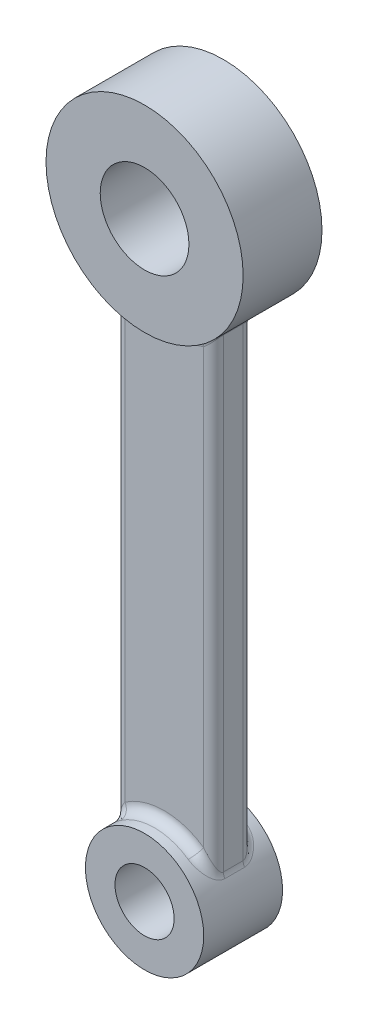
SolidWorks part; units mm, degrees
ref_plane "Front Plane" through (0, 0, 0) normal (0, 0, 1) x (1, 0, 0)
ref_plane "Top Plane" through (0, 0, 0) normal (0, 1, 0) x (1, 0, 0)
ref_plane "Right Plane" through (0, 0, 0) normal (1, 0, 0) x (0, 0, -1)
sketch "Sketch1" plane through (0, 0, 0) normal (0, 1, 0) x (1, 0, 0)
  line L1 (2.5, -1) -> (-2.5, -1)
  line L2 (2.5, -1) -> (2.5, 1)
  line L3 (2.5, 1) -> (-2.5, 1)
  line L4 (-2.5, -1) -> (-2.5, 1)
  line L5 (2.5, -1) -> (-2.5, 1) construction
  line L6 (2.5, 1) -> (-2.5, -1) construction
  point P0 (0, 0)
  dimension "D1" = 5
  dimension "D2" = 2
extrude "Boss-Extrude1" add sketch "Sketch1" along normal mid plane 30
sketch "Sketch2" plane through (0, 0, -1) normal (0, 0, -1) x (-1, 0, 0)
  line L0 (-2.5, -15) -> (2.5, -15) construction
  line L1 (-2.5, 15) -> (2.5, 15) construction
  circle A0 centre (0, -15) radius 3
  circle A1 centre (0, 15) radius 5
  dimension "D1" = 6
  dimension "D2" = 10
sketch "Sketch3" plane through (0, 0, 0) normal (0, 0, 1) x (1, 0, 0)
  circle A0 centre (0, -15) radius 3
  circle A1 centre (0, 15) radius 5
extrude "Boss-Extrude3" add sketch "Sketch3" along normal mid plane 4
sketch "Sketch4" plane through (0, 0, -2) normal (0, 0, -1) x (-1, 0, 0)
  circle A0 centre (0, -15) radius 1.5
  dimension "D1" = 3
extrude "Cut-Extrude1" cut sketch "Sketch4" against normal blind 7
sketch "Sketch5" plane through (0, 0, -2) normal (0, 0, -1) x (-1, 0, 0)
  circle A0 centre (0, 15) radius 2.25
  dimension "D1" = 4.5
extrude "Cut-Extrude2" cut sketch "Sketch5" against normal blind 7
fillet "Fillet1" radius 0.5 4 edges at (-2.5, -1.3359, -1) (-2.5, -1.3359, 1) (2.5, -1.3359, 1) (2.5, -1.3359, -1)
fillet "Fillet2" radius 0.5 16 edges at (2.4123, 10.6204, -0.7829) (2.5, 10.6699, 0) (2.3376, 10.5801, 0.8688) (0, 10, 1) (-2.4123, 10.6204, 0.7829) (-2.5, 10.6699, 0) (-2.3376, 10.5801, -0.8688) (0, 10, -1) (2.3986, -13.1981, -0.8019) (0, -12, -1) (-2.4553, -13.2762, -0.7066) (-2.5, -13.3417, 0) (-2.3986, -13.1981, 0.8019) (0, -12, 1) (2.4553, -13.2762, 0.7066) (2.5, -13.3417, 0)
